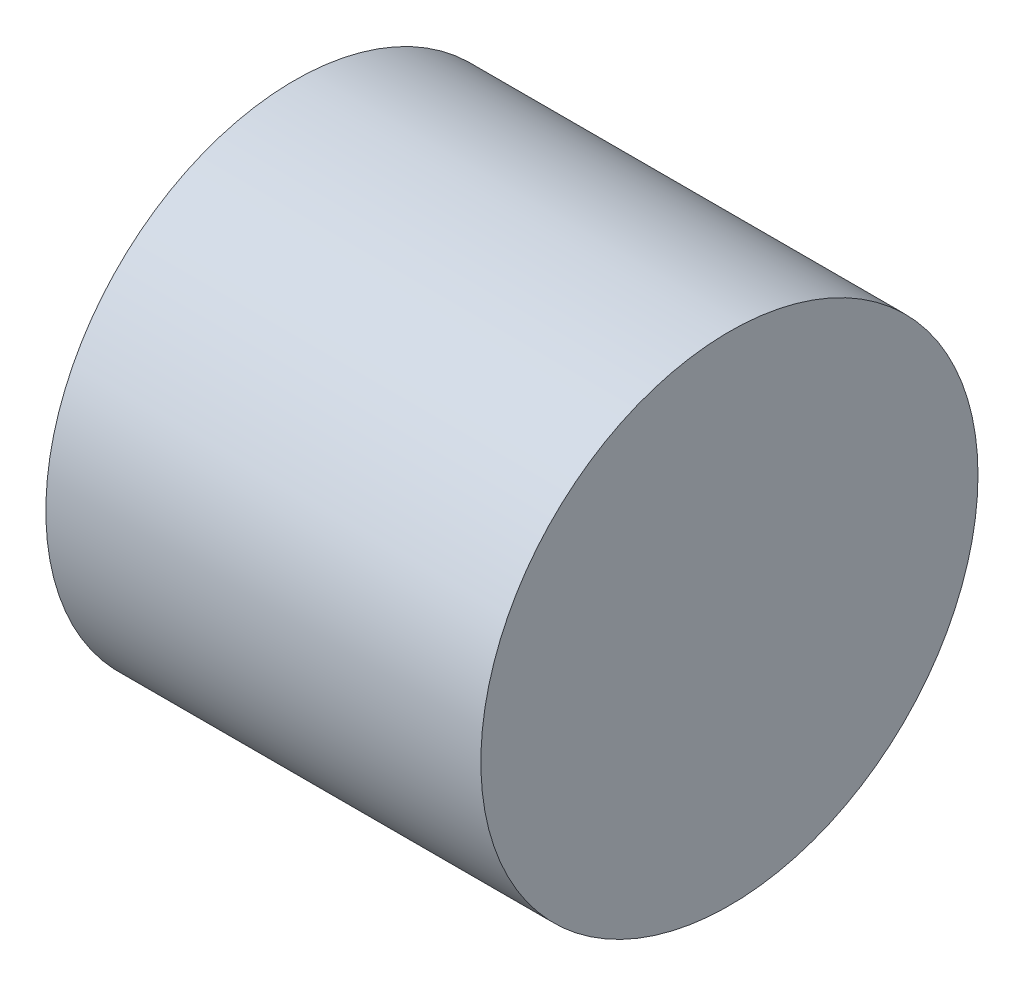
SolidWorks part; units mm, degrees
ref_plane "Front Plane" through (0, 0, 0) normal (0, 0, 1) x (1, 0, 0)
ref_plane "Top Plane" through (0, 0, 0) normal (0, 1, 0) x (1, 0, 0)
ref_plane "Right Plane" through (0, 0, 0) normal (1, 0, 0) x (0, 0, -1)
sketch "Sketch1" plane through (0, 0, 0) normal (1, 0, 0) x (0, 0, -1)
  circle A0 centre (0, 0) radius 50.8
  dimension "D1" = 101.6
extrude "Boss-Extrude1" add sketch "Sketch1" along normal blind 88.9
